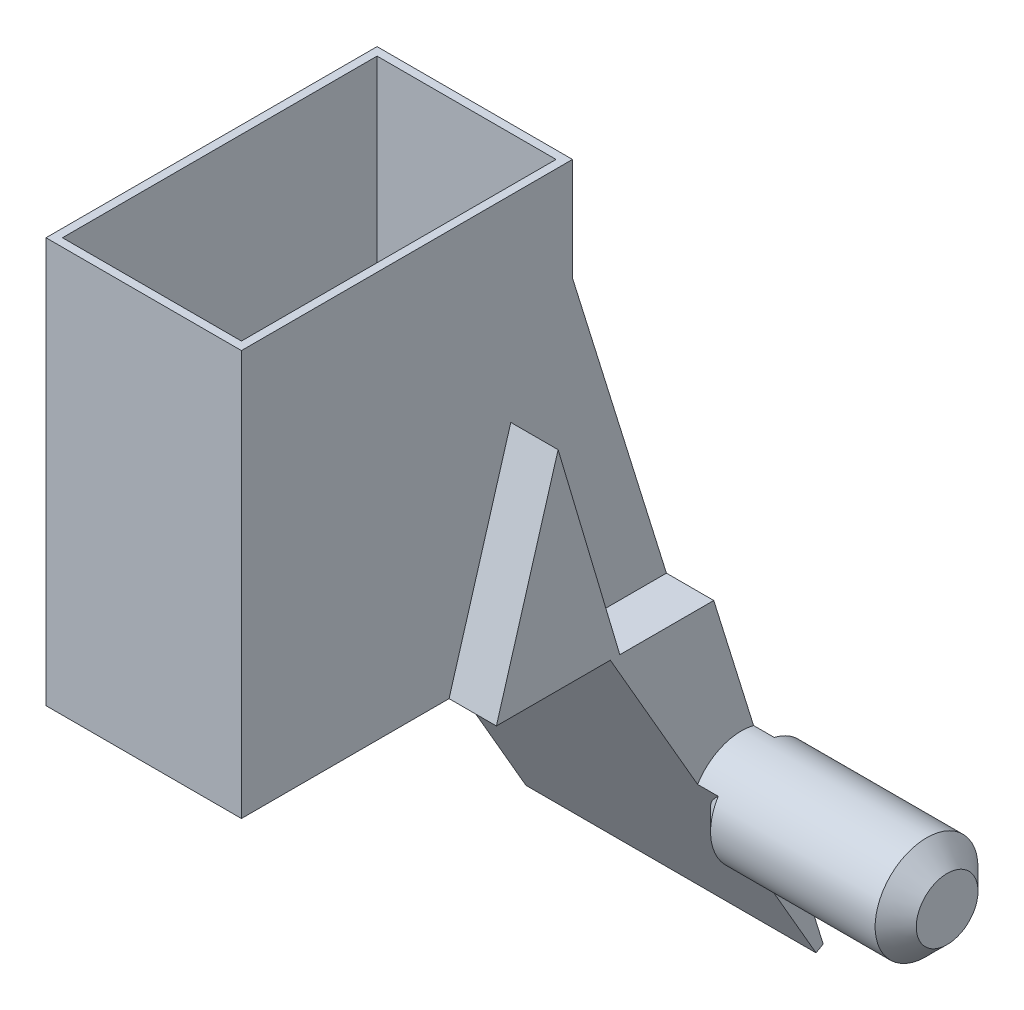
SolidWorks part; units mm, degrees
ref_plane "Ebene vorne" through (0, 0, 0) normal (0, 0, 1) x (1, 0, 0)
ref_plane "Ebene oben" through (0, 0, 0) normal (0, 1, 0) x (1, 0, 0)
ref_plane "Ebene rechts" through (0, 0, 0) normal (1, 0, 0) x (0, 0, -1)
sketch "Skizze1" plane through (0, 0, 0) normal (0, 1, 0) x (1, 0, 0)
  line L1 (0, 0) -> (9.5, 0)
  line L2 (0, 0) -> (0, 16.093)
  line L3 (0, 16.093) -> (9.5, 16.093)
  line L4 (9.5, 0) -> (9.5, 16.093)
  line L15 (0.4, 0.4) -> (0.4, 15.693)
  line L17 (0.4, 15.693) -> (9.1, 15.693)
  line L18 (9.1, 0.4) -> (9.1, 15.693)
  line L19 (0.4, 0.4) -> (9.1, 0.4)
  dimension "D1" = 16.093
  dimension "D2" = 9.5
  dimension "D3" = 0.4
extrude "Aufsatz-Linear austragen1" add sketch "Skizze1" along normal blind 19.7
sketch "Skizze2" plane through (0, 0, 0) normal (-1, 0, 0) x (0, 0, 1)
  line L1 (-16.093, 19.7) -> (-16.093, 0) construction
  line L2 (-16.093, 0) -> (-13.093, 10.13)
  line L3 (-13.093, 10.13) -> (-10.093, 0)
  line L5 (-16.093, 0) -> (0, 0) construction
  line L6 (-10.093, 0) -> (-16.093, 0)
  dimension "D1" = 10.13
  dimension "D2" = 6
  dimension "D3" = 3
extrude "Aufsatz-Linear austragen2" add sketch "Skizze2" along normal blind 2.3
ref_plane "Ebene1" through (4.75, 0, 0) normal (1, 0, 0) x (0, 0, -1)
mirror "Spiegeln1" about plane through (4.75, 0, 0) normal (1, 0, 0) of "Aufsatz-Linear austragen2"
sketch "Skizze5" plane through (-2.3, 0, 0) normal (-1, 0, 0) x (0, 0, 1)
  line L1 (-25.9775, -17.1205) -> (-25.6311, -17.3205)
  line L2 (-25.6311, -17.3205) -> (-15.6311, 0)
  line L3 (-16.093, 0) -> (-10.093, 0) construction
  line L4 (-15.6311, 0) -> (-16.093, 0)
  line L8 (-25.9775, -17.1205) -> (-16.093, 0)
  line L9 (-16.093, 19.7) -> (-16.093, 0) construction
  dimension "D1" = 150
  dimension "D2" = 20
  dimension "D4" = 0.4
extrude "Aufsatz-Linear austragen3" add sketch "Skizze5" against normal up to vertex (14.1 mm away) up to point (11.8, 0, -16.093)
sketch "Skizze6" plane through (0, 0, 0) normal (-1, 0, 0) x (0, 0, 1)
  line L0 (-25.9775, -17.1205) -> (-16.093, 0)
  line L2 (-16.093, 0) -> (-16.093, 14.7)
  line L3 (-16.093, 14.7) -> (-25.9775, -17.1205)
  dimension "D1" = 5
extrude "Aufsatz-Linear austragen4" add sketch "Skizze6" against normal up to vertex (9.5 mm away) up to point (9.5, 0, -16.093)
sketch "Skizze7" plane through (9.5, 0, 0) normal (1, 0, 0) x (0, 0, -1)
  line L0 (25.9775, -17.1205) -> (20.6593, 0)
  line L1 (16.093, 14.7) -> (25.9775, -17.1205) construction
  line L2 (20.6593, 0) -> (15.6311, 0)
  line L8 (25.9775, -17.1205) -> (25.6311, -17.3205)
  line L9 (25.6311, -17.3205) -> (15.6311, 0)
extrude "Aufsatz-Linear austragen5" add sketch "Skizze7" along normal blind 2.3
sketch "Skizze8" plane through (11.8, 0, 0) normal (1, 0, 0) x (0, 0, -1)
  line L0 (25.6311, -17.3205) -> (18.3762, 0) construction
  line L1 (20.6593, 0) -> (16.093, 0) construction
  circle A0 centre (22.0036, -8.6603) radius 2.5
  dimension "D1" = 5
extrude "Aufsatz-Linear austragen6" add sketch "Skizze8" along normal blind 10
chamfer "Fase1" distance 1 angle 45 3 edges at (11.8, -9.9103, -19.8386) (11.8, -7.9186, -24.3911) (21.8, -8.6603, -24.5036)
sketch "Skizze9" plane through (0, 0, 0) normal (-1, 0, 0) x (0, 0, 1)
  line L0 (-16.093, 0) -> (-20.6593, 0)
  line L1 (-20.6593, 0) -> (-25.9775, -17.1205)
  line L2 (-25.9775, -17.1205) -> (-16.093, 0)
extrude "Aufsatz-Linear austragen7" add sketch "Skizze9" along normal blind 2.3
sketch "Skizze10" plane through (-2.3, 0, 0) normal (-1, 0, 0) x (0, 0, 1)
  circle A0 centre (-22.0036, -8.6603) radius 2.5
  dimension "D1" = 5
extrude "Aufsatz-Linear austragen8" add sketch "Skizze10" along normal blind 10
chamfer "Fase2" distance 1 angle 45 3 edges at (-12.3, -8.6603, -19.5036) (-2.3, -7.9186, -24.3911) (-2.3, -9.9103, -19.8386)
